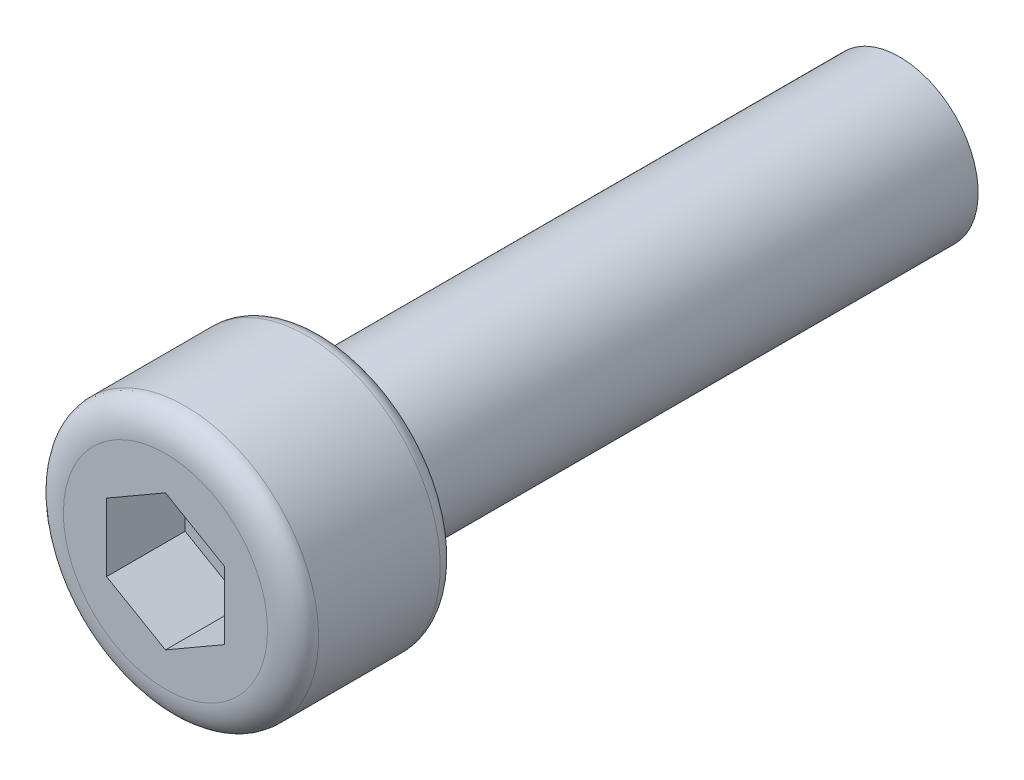
SolidWorks part; units mm, degrees
ref_plane "前视基准面" through (0, 0, 0) normal (0, 0, 1) x (1, 0, 0)
ref_plane "上视基准面" through (0, 0, 0) normal (0, 1, 0) x (1, 0, 0)
ref_plane "右视基准面" through (0, 0, 0) normal (1, 0, 0) x (0, 0, -1)
sketch "草图2" plane through (0, 0, 0) normal (1, 0, 0) x (0, 0, -1)
  line L0 (-9.5, 0) -> (-9.5, 3.4)
  line L1 (-9.5, 3.4) -> (-5.5, 3.4)
  line L2 (-5.5, 3.4) -> (-5.5, 2)
  line L3 (-5.5, 2) -> (9.5, 2)
  line L4 (9.5, 2) -> (9.5, 0)
  line L5 (9.5, 0) -> (-9.5, 0)
  dimension "D1" = 15
  dimension "D2" = 3.4
  dimension "D3" = 2
  dimension "D4" = 4
revolve "旋转1" add sketch "草图2" angle 360 about L5
chamfer "倒角1" distance 0.3 angle 60 1 edges at (-2, 0, -9.5) first distance on face at (-2, 0, 5.5)
fillet "圆角1" radius 0.4 1 edges at (-3.4, 0, 5.5)
fillet "圆角2" radius 0.8 1 edges at (-3.4, 0, 9.5) second distance 0.5 first distance on face at (-3.4, 0, 9.5)
sketch "草图3" plane through (0, 0, 9.5) normal (0, 0, 1) x (1, 0, 0)
  line L1 (0, 1.7321) -> (-1.5, 0.866)
  line L2 (-1.5, 0.866) -> (-1.5, -0.866)
  line L3 (-1.5, -0.866) -> (0, -1.7321)
  line L4 (0, -1.7321) -> (1.5, -0.866)
  line L5 (1.5, -0.866) -> (1.5, 0.866)
  line L6 (1.5, 0.866) -> (0, 1.7321)
  circle A0 centre (0, 0) radius 1.5 construction
  dimension "D1" = 3
extrude "切除-拉伸1" cut sketch "草图3" against normal blind 2
